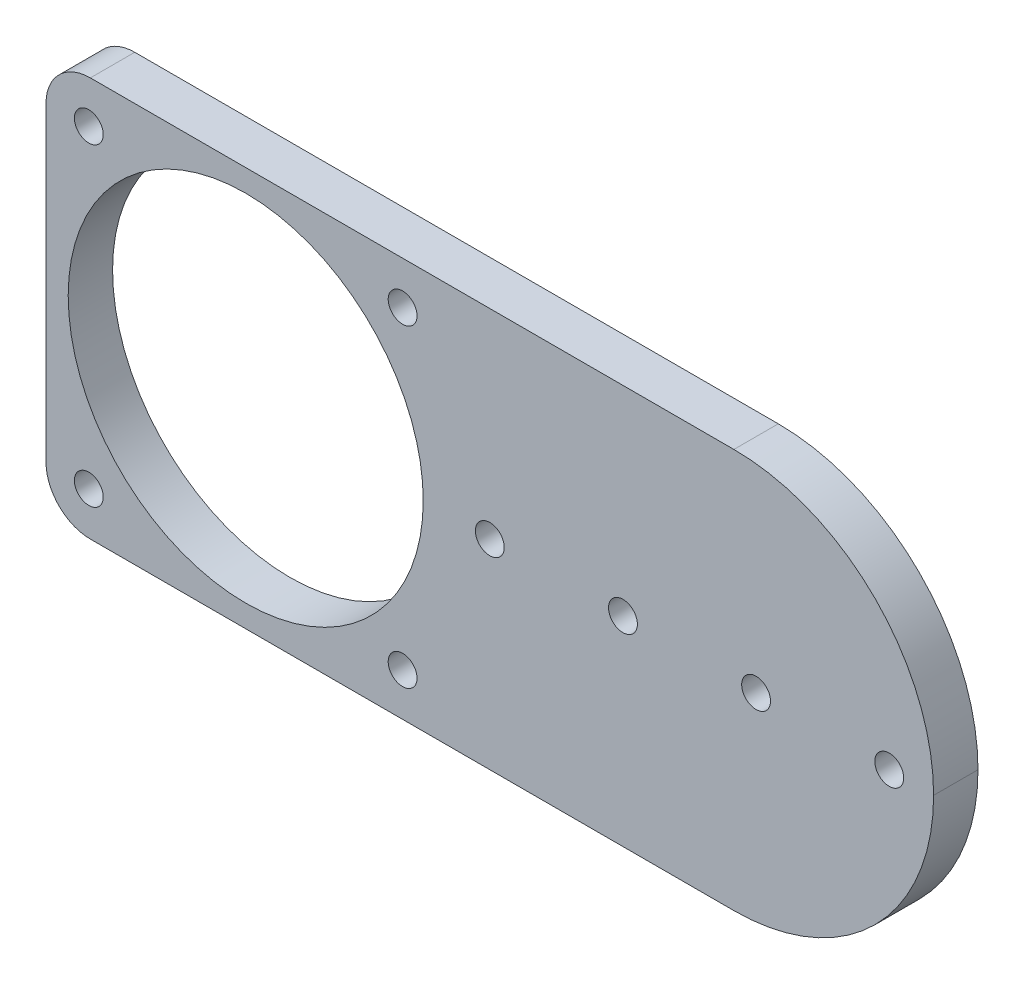
SolidWorks part; units mm, degrees
ref_plane "Front Plane" through (0, 0, 0) normal (0, 0, 1) x (1, 0, 0)
ref_plane "Top Plane" through (0, 0, 0) normal (0, 1, 0) x (1, 0, 0)
ref_plane "Right Plane" through (0, 0, 0) normal (1, 0, 0) x (0, 0, -1)
sketch "Sketch1" plane through (0, 0, 0) normal (0, 0, 1) x (1, 0, 0)
  line L0 (-59.7548, 0) -> (-14.7548, 0) construction
  line L1 (-59.7548, 45) -> (140.2452, 45)
  line L2 (-59.7548, 45) -> (-59.7548, -45)
  line L3 (-59.7548, -45) -> (140.2452, -45)
  line L4 (140.2452, 45) -> (140.2452, -45)
  line L9 (-14.7548, 0) -> (-50.1101, 35.3553) construction
  line L10 (-14.7548, 0) -> (20.6006, -35.3553) construction
  line L12 (-50.1101, 35.3553) -> (20.6006, 35.3553) construction
  line L13 (-50.1101, 35.3553) -> (-50.1101, -35.3553) construction
  line L14 (-50.1101, -35.3553) -> (20.6006, -35.3553) construction
  line L15 (20.6006, 35.3553) -> (20.6006, -35.3553) construction
  circle A0 centre (-14.7548, 0) radius 50 construction
  circle A1 centre (-50.1101, 35.3553) radius 3.25
  circle A2 centre (20.6006, 35.3553) radius 3.25
  circle A3 centre (20.6006, -35.3553) radius 3.25
  circle A4 centre (-50.1101, -35.3553) radius 3.25
  circle A5 centre (-14.7548, 0) radius 40
  circle A6 centre (40.2452, 0) radius 3.25
  circle A7 centre (70.2452, 0) radius 3.25
  circle A8 centre (100.2452, 0) radius 3.25
  circle A9 centre (130.2452, 0) radius 3.25
  point P0 (0, 0)
  dimension "D4" = 45
  dimension "D5" = 100
  dimension "D7" = 6.5
  dimension "D8" = 6.5
  dimension "D1" = 90
  dimension "D2" = 200
  dimension "D3" = 45
  dimension "D6" = 4
extrude "Boss-Extrude1" add sketch "Sketch1" along normal blind 10
fillet "Fillet1" radius 45 2 edges at (140.2452, -45, 5) (140.2452, 45, 5)
fillet "Fillet2" radius 10 2 edges at (-59.7548, -45, 5) (-59.7548, 45, 5)
